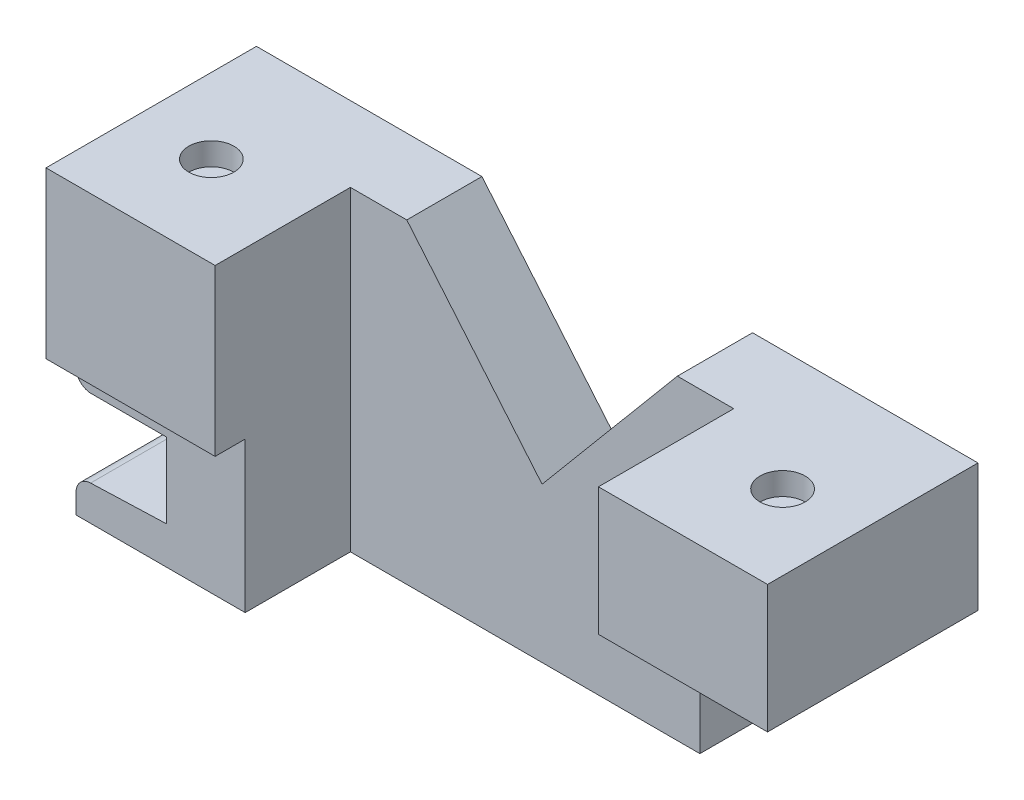
SolidWorks part; units mm, degrees
ref_plane "Front Plane" through (0, 0, 0) normal (0, 0, 1) x (1, 0, 0)
ref_plane "Top Plane" through (0, 0, 0) normal (0, 1, 0) x (1, 0, 0)
ref_plane "Right Plane" through (0, 0, 0) normal (1, 0, 0) x (0, 0, -1)
sketch "Sketch2" plane through (0, 0, 0) normal (0, 0, 1) x (1, 0, 0)
  line L1 (-12, 3) -> (-12, 12)
  line L2 (-12, 12) -> (-24, 12)
  line L3 (-24, 12) -> (-24, 0)
  line L4 (-24, 0) -> (24, 0)
  line L5 (24, 0) -> (24, 12)
  line L6 (12, 3) -> (-12, 3)
  line L8 (0, 0) -> (0, 3) construction
  line L9 (12, 3) -> (12, 12)
  line L10 (12, 12) -> (24, 12)
  dimension "D3" = 3
  dimension "D1" = 48
  dimension "D2" = 9
  dimension "D5" = 12
extrude "Boss-Extrude1" add sketch "Sketch2" along normal mid plane 19 contours L4 L8 L6 L1 L2 L3 | L8 L4 L5 L6 region at (-15.6, 5.1, 0) region at (15.6, 5.1, 0)
sketch "Sketch3" plane through (0, 0, 9.5) normal (0, 0, 1) x (1, 0, 0)
  line L0 (-2.6212, 0) -> (-0.8192, -2.5736)
  line L1 (-24, 0) -> (24, 0) construction
  line L2 (0.8192, -2.5736) -> (2.6212, 0)
  line L3 (2.6212, 0) -> (-2.6212, 0)
  line L4 (0, -3.7434) -> (0, 0) construction
  arc A0 (-0.8192, -2.5736) -> (0.8192, -2.5736) centre (0, -2) ccw
  dimension "D1" = 1
  dimension "D3" = 3
  dimension "D2" = 70
extrude "Boss-Extrude2" [suppressed] add sketch "Sketch3" against normal up to surface (18 mm away) up to face at (0, 6.75, -9.5)
sketch "Sketch4" plane through (24, 0, 0) normal (1, 0, 0) x (0, 0, -1)
  line L4 (9.5, 0) -> (9.5, 12)
  line L5 (9.5, 12) -> (-9.5, 12)
  line L6 (-9.5, 12) -> (-9.5, 0)
  line L7 (-9.5, 0) -> (9.5, 0)
  line L8 (9.5, 0) -> (9.5, 12)
  line L10 (-9.5, 12) -> (-9.5, 0)
  line L11 (-9.5, 0) -> (9.5, 0)
  line L12 (9.5, 12) -> (-9.5, 12)
  dimension "D1" = 0
sketch "Sketch5" plane through (0, 12, 0) normal (0, 1, 0) x (1, 0, 0)
  line L0 (-19, 1.5) -> (19, 1.5) construction
  line L1 (0, 1.5) -> (0, 0) construction
  circle A0 centre (-19, 1.5) radius 1.5
  circle A1 centre (19, 1.5) radius 1.5
  dimension "D1" = 3
  dimension "D2" = 38
  dimension "D3" = 1.5
extrude "Cut-Extrude1" cut sketch "Sketch5" against normal blind 1.5
sketch "Sketch9" plane through (0, 0, 0) normal (0, -1, 0) x (1, 0, 0)
  line L0 (-24, -9.5) -> (24, -9.5) construction
  line L1 (-10.5, -4.5) -> (10.5, -4.5)
  line L2 (-10.5, -4.5) -> (-10.5, -9.5)
  line L3 (-10.5, -9.5) -> (10.5, -9.5)
  line L4 (10.5, -4.5) -> (10.5, -9.5)
  line L5 (0, -9.5) -> (0, -4.5) construction
  line L6 (-10.5, -7) -> (10.5, -7) construction
  line L7 (0, 0) -> (0, -4.5) construction
  point P128 (0, -7)
  dimension "D1" = 5
  dimension "D2" = 21
extrude "Boss-Extrude6" add sketch "Sketch9" along normal blind 9
sketch "Sketch10" plane through (0, 0, 0) normal (0, -1, 0) x (1, 0, 0)
  line L0 (-24, 9.5) -> (24, 9.5) construction
  line L1 (-10.5, -4.5) -> (10.5, -4.5)
  line L2 (-10.5, -4.5) -> (-10.5, 9.5)
  line L3 (-10.5, 9.5) -> (10.5, 9.5)
  line L4 (10.5, -4.5) -> (10.5, 9.5)
  line L5 (0, 9.5) -> (0, -4.5) construction
  line L6 (-10.5, 2.5) -> (10.5, 2.5) construction
  point P136 (0, 2.5)
extrude "Cut-Extrude4" cut sketch "Sketch10" against normal through all
sketch "Sketch11" plane through (0, 0, 9.5) normal (0, 0, 1) x (1, 0, 0)
  line L6 (10.5, 3) -> (10.5, 0)
  line L7 (10.5, 0) -> (24, 0)
  line L8 (24, 0) -> (24, 12)
  line L9 (24, 12) -> (12, 12)
  line L10 (12, 12) -> (12, 3)
  line L11 (12, 3) -> (10.5, 3)
  line L12 (10.5, 3) -> (10.5, 0)
  line L13 (10.5, 0) -> (24, 0)
  line L14 (24, 0) -> (24, 12)
  line L15 (24, 12) -> (12, 12)
  line L16 (12, 12) -> (12, 3)
  line L17 (12, 3) -> (10.5, 3)
  line L18 (-10.5, 0) -> (-10.5, 3)
  line L19 (-10.5, 3) -> (-12, 3)
  line L20 (-12, 3) -> (-12, 12)
  line L21 (-12, 12) -> (-24, 12)
  line L22 (-24, 12) -> (-24, 0)
  line L23 (-24, 0) -> (-10.5, 0)
  line L24 (-10.5, 0) -> (-10.5, 3)
  line L25 (-10.5, 3) -> (-12, 3)
  line L26 (-12, 3) -> (-12, 12)
  line L27 (-12, 12) -> (-24, 12)
  line L28 (-24, 12) -> (-24, 0)
  line L29 (-24, 0) -> (-10.5, 0)
  dimension "D1" = 0
  dimension "D2" = 0
extrude "Cut-Extrude5" cut sketch "Sketch11" against normal blind 5
sketch "Sketch12" plane through (0, 0, -9.5) normal (0, 0, -1) x (-1, 0, 0)
  line L1 (-12, 3) -> (12, 3)
  line L2 (-12, 3) -> (-12, 12)
  line L3 (-12, 12) -> (12, 12)
  line L4 (12, 3) -> (12, 12)
  line L5 (0, 12) -> (0, 3) construction
  line L6 (-12, 7.5) -> (12, 7.5) construction
  point P184 (0, 7.5)
extrude "Boss-Extrude7" add sketch "Sketch12" against normal blind 5
sketch "Sketch13" plane through (0, 0, -4.5) normal (0, 0, 1) x (1, 0, 0)
  line L0 (-9, 12) -> (0, 1.2742)
  line L1 (-12, 12) -> (12, 12) construction
  line L2 (0, 1.2742) -> (9, 12)
  line L3 (9, 12) -> (-9, 12)
  line L4 (0, 1.2742) -> (0, 12) construction
  dimension "D1" = 50
  dimension "D2" = 18
extrude "Cut-Extrude6" cut sketch "Sketch13" against normal blind 6
sketch "Sketch15" plane through (0, 0, -4.5) normal (0, 0, 1) x (1, 0, 0)
  line L0 (-24, 12) -> (-24, 0) construction
  line L1 (-24, 3.5) -> (24, 3.5)
  line L2 (-24, 3.5) -> (-24, 0)
  line L3 (-24, 0) -> (24, 0)
  line L4 (24, 3.5) -> (24, 0)
  line L5 (0, 0) -> (0, 3.5) construction
  line L6 (-24, 1.75) -> (24, 1.75) construction
  line L7 (20.5, 10.5) -> (17.5, 10.5) construction
  point P224 (0, 1.75)
  dimension "D1" = 7
extrude "Cut-Extrude7" cut sketch "Sketch15" along normal blind 16.5
sketch "Sketch16" plane through (0, 0, -4.5) normal (0, 0, 1) x (1, 0, 0)
  line L1 (-10.5, 0) -> (-24, 0)
  line L2 (-10.5, 0) -> (-10.5, 3.5)
  line L3 (-10.5, 3.5) -> (-24, 3.5)
  line L4 (-24, 0) -> (-24, 3.5)
  line L5 (-17.25, 3.5) -> (-17.25, 0) construction
  line L6 (-10.5, 1.75) -> (-24, 1.75) construction
  line L7 (10.5, 0) -> (24, 0)
  line L8 (10.5, 0) -> (10.5, 3.5)
  line L9 (10.5, 3.5) -> (24, 3.5)
  line L10 (24, 0) -> (24, 3.5)
  line L11 (17.25, 3.5) -> (17.25, 0) construction
  line L12 (10.5, 1.75) -> (24, 1.75) construction
  point P116 (-17.25, 1.75)
  point P143 (17.25, 1.75)
extrude "Cut-Extrude8" cut sketch "Sketch16" against normal blind 16.5
sketch "Sketch17" plane through (0, 0, -9.5) normal (0, 0, -1) x (-1, 0, 0)
  line L0 (0, 0) -> (0, -9) construction
  line L1 (10.5, -9) -> (-10.5, -9) construction
  line L19 (10.5, 3.5) -> (24, 3.5)
  line L20 (10.5, -9) -> (10.5, 3.5)
  line L21 (24, -9) -> (10.5, -9)
  line L22 (24, -6.7095) -> (24, -9)
  line L23 (18, -6.5) -> (24, -6.7095)
  line L24 (18, -1.5) -> (18, -6.5)
  line L25 (24, -1.5) -> (18, -1.5)
  line L26 (24, 3.5) -> (24, -1.5)
  line L27 (10.5, -9) -> (10.5, 3.5) construction
  line L28 (24, 12) -> (24, 3.5) construction
  line L29 (10.5, 3.5) -> (24, 3.5) construction
  dimension "D3" = 5
  dimension "D1" = 2
  dimension "D2" = 6
  dimension "D4" = 5
extrude "Boss-Extrude8" add sketch "Sketch17" against normal up to surface (5 mm away) up to face at (0, 4.1158, -4.5)
sketch "Sketch18" plane through (0, 0, -4.5) normal (0, 0, 1) x (1, 0, 0)
  line L0 (-12, 12) -> (-24, 12) construction
  line L1 (-12.75, 12) -> (12.75, 12)
  line L2 (-12.75, 12) -> (-12.75, 3.5)
  line L3 (-12.75, 3.5) -> (12.75, 3.5)
  line L4 (12.75, 12) -> (12.75, 3.5)
  line L5 (0, 3.5) -> (0, 12) construction
  line L6 (-12.75, 7.75) -> (12.75, 7.75) construction
  line L8 (12, 3.5) -> (24, 3.5) construction
  point P164 (0, 7.75)
  dimension "D1" = 12.75
extrude "Cut-Extrude9" cut sketch "Sketch18" along normal up to surface (9 mm away) up to face at (-18, 7.75, 4.5)
sketch "Sketch19" plane through (0, 0, -4.5) normal (0, 0, 1) x (1, 0, 0)
  line L2 (-24, 3.5) -> (-12.75, 3.5)
  line L3 (-12.75, 3.5) -> (-12.75, -9)
  line L4 (10.5, -9) -> (-24, -9) construction
  line L11 (-9, 12) -> (-12.75, 12)
  line L12 (-12.75, 12) -> (-12.75, 3.5)
  line L13 (-12.75, 3.5) -> (-24, 3.5)
  line L14 (-24, 3.5) -> (-24, -1.5)
  line L15 (-24, -9) -> (10.5, -9)
  line L17 (10.5, 3.5) -> (12.75, 3.5)
  line L18 (12.75, 3.5) -> (12.75, 12)
  line L19 (12.75, 12) -> (9, 12)
  line L20 (9, 12) -> (0, 1.2742)
  line L21 (0, 1.2742) -> (-9, 12)
  line L38 (-24, 3.5) -> (-24, -1.5)
  line L40 (-24, -1.5) -> (-18, -1.5)
  line L42 (-24, -1.5) -> (-18, -1.5)
  line L44 (-18, -1.5) -> (-18, -6.5)
  line L48 (-18, -1.5) -> (-18, -6.5)
  line L49 (-18, -6.5) -> (-24, -6.7095)
  line L50 (-18, -6.5) -> (-24, -6.7095)
  line L51 (-24, -6.7095) -> (-24, -9)
  line L52 (-24, -6.7095) -> (-24, -9)
  line L53 (10.5, -9) -> (10.5, 3.5)
  line M16 (-12.75, 3.5) -> (-24, 3.5)
  line M19 (-24, -9) -> (10.5, -9)
  line M38 (-24, 3.5) -> (-24, -1.5)
  line M39 (-24, -1.5) -> (-18, -1.5)
  line M40 (-18, -1.5) -> (-18, -6.5)
  line M41 (-18, -6.5) -> (-24, -6.7095)
  line M42 (-24, -6.7095) -> (-24, -9)
  dimension "D1" = 0
extrude "Boss-Extrude9" add sketch "Sketch19" along normal up to surface (9 mm away) contours L3 M16 M38 M39 M40 M41 M42 M19 region at (-17.6384, -2.3873, -4.5) up to face at (-18.375, 7.75, 4.5)
fillet "Fillet1" radius 1 2 edges at (-24, -1.5, -2.5) (-24, -6.7095, -2.5)
sketch "Sketch20" plane through (0, 0, 4.5) normal (0, 0, 1) x (1, 0, 0)
  line L0 (-24, 12) -> (-24, -0.5) construction
  line L1 (-12.75, -9) -> (-24, -9)
  line L2 (-12.75, -9) -> (-12.75, 1)
  line L3 (-12.75, 1) -> (-24, 1)
  line L4 (-24, -9) -> (-24, 1)
  line L5 (-18.375, 1) -> (-18.375, -9) construction
  line L6 (-12.75, -4) -> (-24, -4) construction
  point P208 (-18.375, -4)
  dimension "D1" = 10
extrude "Cut-Extrude10" cut sketch "Sketch20" against normal blind 2
